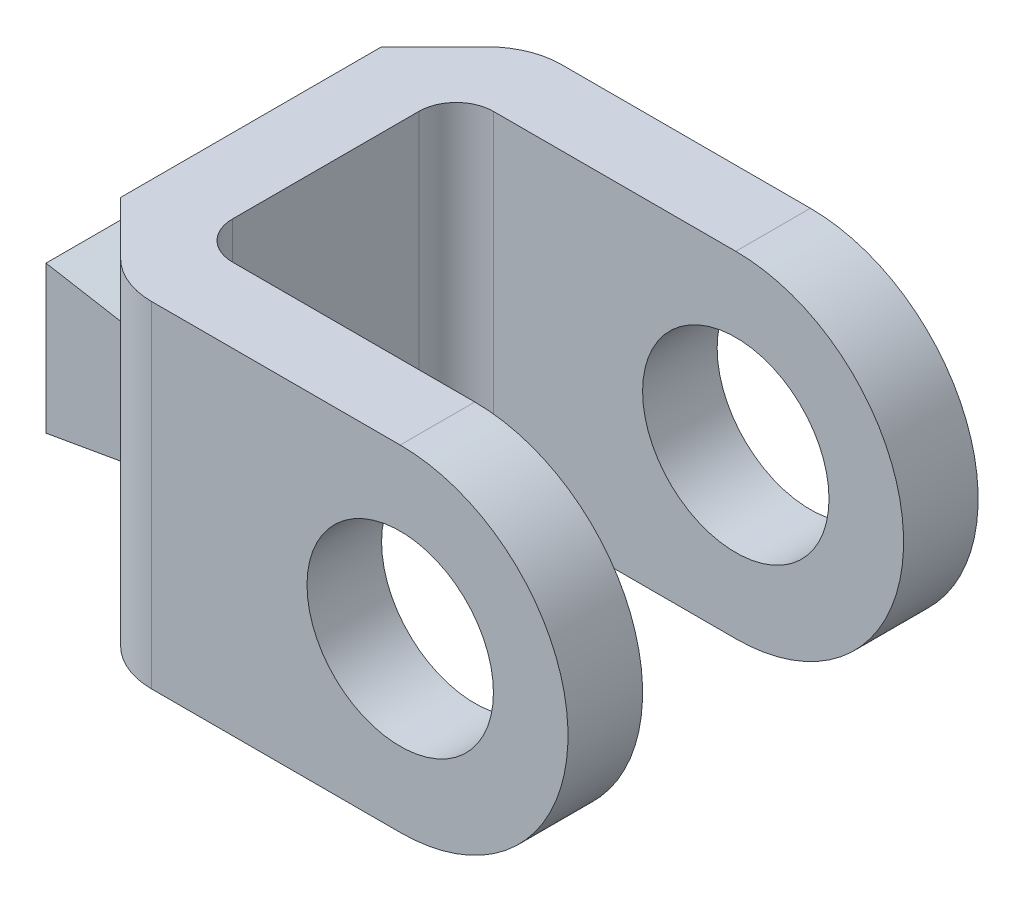
SolidWorks part; units mm, degrees
ref_plane "Front Plane" through (0, 0, 0) normal (0, 0, 1) x (1, 0, 0)
ref_plane "Top Plane" through (0, 0, 0) normal (0, 1, 0) x (1, 0, 0)
ref_plane "Right Plane" through (0, 0, 0) normal (1, 0, 0) x (0, 0, -1)
sketch "Sketch1" plane through (0, 0, 0) normal (0, 0, 1) x (1, 0, 0)
  line L0 (-7.1268, 0) -> (0, 0) construction
  line L1 (0, -4.5) -> (0, -1.625) construction
  line L2 (0, -1.625) -> (-2, -1.975)
  line L6 (-2, -1.975) -> (-2, 1.975)
  line L7 (0, 0) -> (-2, 1.975) construction
  line L8 (0, 0) -> (-2, -1.975) construction
  line L9 (0, 1.625) -> (-2, 1.975)
  line L11 (0, 0) -> (6.5352, 0) construction
  line L12 (0, 1.625) -> (0, 4.5)
  line L13 (0, -4.5) -> (2, -4.5)
  line L14 (0, -4.5) -> (0, -1.625)
  line L15 (0, 4.5) -> (2, 4.5)
  line L16 (2, -4.5) -> (2, 4.5)
  line L17 (0, 1.625) -> (0, 4.499) construction
  point P5 (0, 0)
  point P10 (0, 1.625)
  point P12 (0, -1.625)
  point P16 (-2, 0)
  dimension "D1" = 2
  dimension "D2" = 3.95
  dimension "D3" = 9
  dimension "D4" = 4.5
  dimension "D5" = 3.25
extrude "Boss-Extrude2" add sketch "Sketch1" along normal blind 7
sketch "Sketch2" plane through (0, 0, 0) normal (0, 0, 1) x (1, 0, 0)
  line L1 (0, 4.5) -> (9.5, 4.5)
  line L2 (0, 4.5) -> (0, -4.5)
  line L3 (0, -4.5) -> (9.5, -4.5)
  arc A0 (9.5, -4.5) -> (9.5, 4.5) centre (9.5, 0) ccw
  circle A1 centre (9.5, 0) radius 2.5
  circle A2 centre (9.5, 0) radius 6.5 construction
  point P1 (14, 0)
  point P11 (3, 0)
  dimension "D3" = 5
  dimension "D2" = 13
  dimension "D1" = 14
extrude "Boss-Extrude3" add sketch "Sketch2" against normal blind 2
ref_plane "Plane1" through (0, 4.5, 0) normal (0, 1, 0) x (1, 0, 0)
sketch "Sketch4" plane through (0, 4.5, 0) normal (0, 1, 0) x (1, 0, 0)
  line L0 (2, 0) -> (2, 2.9724) construction
  line L1 (9.5, 2) -> (0, 2) construction
  line L2 (0, 0) -> (2, 2)
  line L3 (2, 2) -> (0, 2)
  line L4 (0, 0) -> (0, 2)
  point P0 (2, 0)
  point P4 (2, 2)
extrude "Cut-Extrude3" cut sketch "Sketch4" against normal through all
fillet "Fillet1" radius 1 1 edges at (2, 0, 0)
fillet "Fillet2" radius 2 1 edges at (2, 0, -2)
ref_plane "Plane2" through (0, 0, 3.5) normal (0, 0, 1) x (1, 0, 0)
mirror "Mirror2" about plane through (0, 0, 3.5) normal (0, 0, 1) of "Boss-Extrude2", "Fillet2", "Cut-Extrude3", "Boss-Extrude3"
fillet "Fillet3" radius 1 1 edges at (2, 0, 7)
